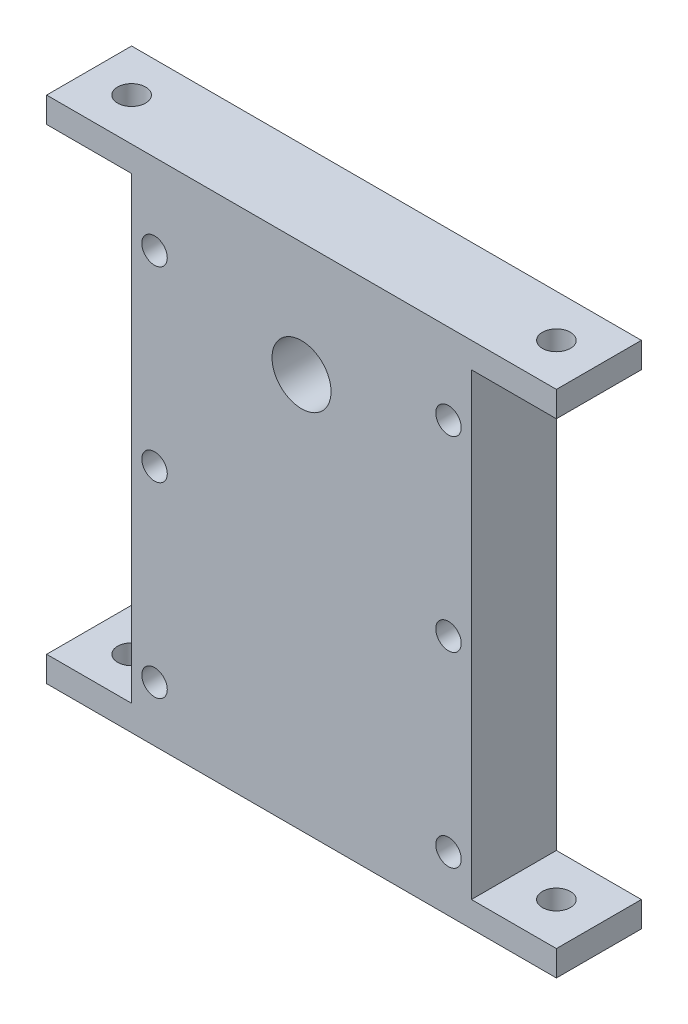
SolidWorks part; units mm, degrees
ref_plane "Front Plane" through (0, 0, 0) normal (0, 0, 1) x (1, 0, 0)
ref_plane "Top Plane" through (0, 0, 0) normal (0, 1, 0) x (1, 0, 0)
ref_plane "Right Plane" through (0, 0, 0) normal (1, 0, 0) x (0, 0, -1)
sketch "Sketch1" plane through (0, 0, 0) normal (0, 0, 1) x (1, 0, 0)
  line L1 (-20, 30) -> (20, 30)
  line L2 (-20, 30) -> (-20, -30)
  line L3 (-20, -30) -> (20, -30)
  line L4 (20, 30) -> (20, -30)
  line L5 (0, -33) -> (0, 33) construction
  circle A0 centre (0, 16.5) radius 3.475
  circle A1 centre (-17.3, -1.5) radius 1.5
  circle A2 centre (-17.3, 20.5) radius 1.5
  circle A3 centre (17.3, -1.5) radius 1.5
  circle A4 centre (17.3, 20.5) radius 1.5
  circle A5 centre (-17.3, -23.5) radius 1.5
  circle A6 centre (17.3, -23.5) radius 1.5
  point P0 (0, 0)
  dimension "D4" = 6.95
  dimension "D10" = 3
  dimension "D11" = 3
  dimension "D12" = 3
  dimension "D1" = 40
  dimension "D2" = 60
  dimension "D3" = 46.5
  dimension "D5" = 30
  dimension "D6" = 20
  dimension "D7" = 28.5
  dimension "D8" = 17.3
  dimension "D9" = 22
  dimension "D13" = 22
extrude "Boss-Extrude1" add sketch "Sketch1" along normal blind 10
sketch "Esquisse1" plane through (20, 0, 0) normal (1, 0, 0) x (0, 0, -1)
  line L0 (0, 30) -> (-10, 30)
  line L1 (-10, 30) -> (-10, 27)
  line L2 (-10, -30) -> (-10, 30) construction
  line L3 (-10, 27) -> (0, 27)
  line L4 (0, -30) -> (0, 30) construction
  line L5 (0, 27) -> (0, 30)
  line L6 (0, -30) -> (0, -27)
  line L7 (0, -27) -> (-10, -27)
  line L8 (-10, -27) -> (-10, -30)
  line L9 (-10, -30) -> (0, -30)
  dimension "D1" = 3
  dimension "D2" = 3
extrude "Boss.-Extru.1" add sketch "Esquisse1" along normal blind 10
sketch "Esquisse2" plane through (-20, 0, 0) normal (-1, 0, 0) x (0, 0, 1)
  line L0 (0, 30) -> (10, 30)
  line L1 (10, 30) -> (10, 27)
  line L2 (10, 27) -> (0, 27)
  line L3 (0, 30) -> (0, -30) construction
  line L4 (0, 27) -> (0, 30)
  line L5 (10, 30) -> (10, -30) construction
  line L6 (0, -30) -> (10, -30)
  line L7 (0, -30) -> (0, -27)
  line L8 (0, -27) -> (10, -27)
  line L9 (10, -30) -> (10, -27)
  dimension "D1" = 3
  dimension "D2" = 3
extrude "Boss.-Extru.2" add sketch "Esquisse2" along normal blind 10
sketch "Esquisse3" plane through (0, 27, 0) normal (0, -1, 0) x (1, 0, 0)
  line L0 (0, -33) -> (0, 33) construction
  circle A0 centre (-25, 5) radius 1.65
  circle A1 centre (25, 5) radius 1.65
  dimension "D3" = 3.3
  dimension "D1" = 5
  dimension "D2" = 5
extrude "Enlèv. mat.-Extru.1" cut sketch "Esquisse3" against normal through all both and the other way through all
